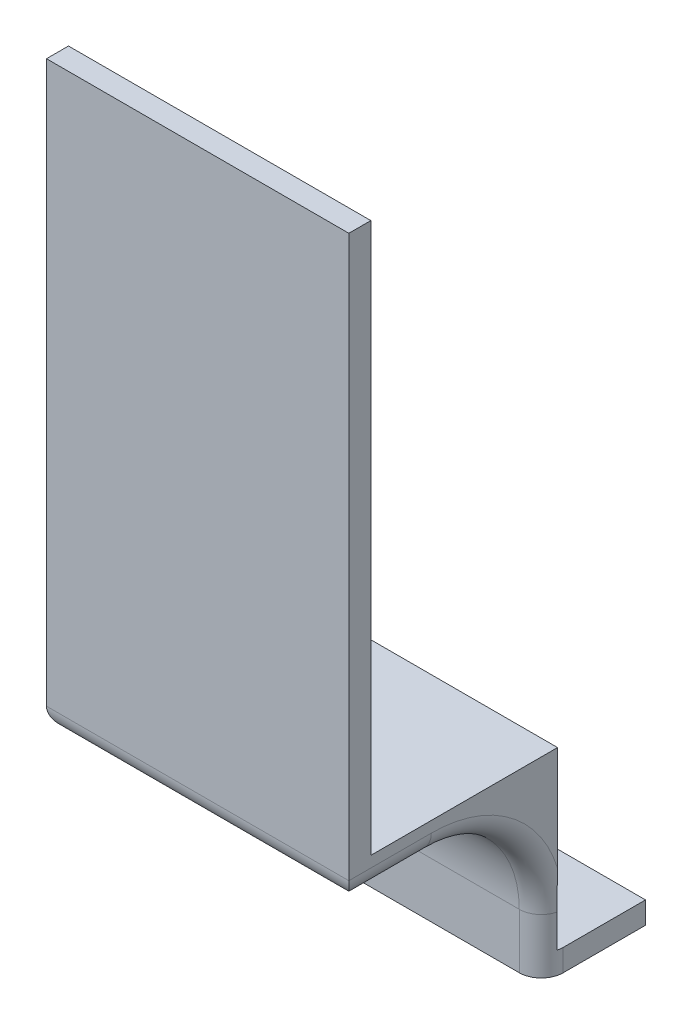
SolidWorks part; units mm, degrees
material "PET"
ref_plane "前视基准面" through (0, 0, 0) normal (0, 0, 1) x (1, 0, 0)
ref_plane "上视基准面" through (0, 0, 0) normal (0, 1, 0) x (1, 0, 0)
ref_plane "右视基准面" through (0, 0, 0) normal (1, 0, 0) x (0, 0, -1)
other "Configuration Table"
sketch "草图1" plane through (0, 0, 0) normal (0, 1, 0) x (1, 0, 0)
  line L1 (-15, 5.5) -> (15, 5.5)
  line L2 (-15, 5.5) -> (-15, -5.5)
  line L3 (-15, -5.5) -> (15, -5.5)
  line L4 (15, 5.5) -> (15, -5.5)
  line L5 (-15, 5.5) -> (15, -5.5) construction
  line L6 (-15, -5.5) -> (15, 5.5) construction
  point P0 (0, 0)
  dimension "D1" = 30
  dimension "D2" = 11
extrude "凸台-拉伸1" add sketch "草图1" along normal blind 6
sketch "草图2" plane through (-15, 0, 0) normal (-1, 0, 0) x (0, 0, 1)
  line L0 (-5.5, 6) -> (-5.5, 0) construction
  line L1 (-13.5, 2) -> (2.5, 2)
  line L2 (-13.5, 2) -> (-13.5, 4)
  line L3 (-13.5, 4) -> (2.5, 4)
  line L4 (2.5, 2) -> (2.5, 4)
  line L5 (-13.5, 2) -> (2.5, 4) construction
  line L6 (-13.5, 4) -> (2.5, 2) construction
  line L7 (-5.5, 6) -> (5.5, 6) construction
  line L8 (5.5, 6) -> (5.5, 0) construction
  point P0 (-5.5, 3)
  dimension "D1" = 2
  dimension "D2" = 3
extrude "切除-拉伸1" cut sketch "草图2" against normal blind 144
sketch "草图3" plane through (0, 6, 0) normal (0, 1, 0) x (1, 0, 0)
  line L0 (2, 5.5) -> (-2, 5.5)
  line L1 (15, 5.5) -> (-15, 5.5) construction
  line L2 (-2, 5.5) -> (-2, -3.5)
  line L3 (-2, -3.5) -> (-15, -3.5)
  line L4 (-15, 5.5) -> (-15, -5.5) construction
  line L5 (-15, -3.5) -> (-15, -5.5)
  line L6 (-15, -5.5) -> (15, -5.5)
  line L7 (-15, -5.5) -> (15, -5.5) construction
  line L8 (0, 5.5) -> (0, -5.5) construction
  line L9 (15, -3.5) -> (15, -5.5)
  line L10 (2, -3.5) -> (15, -3.5)
  line L11 (2, 5.5) -> (2, -3.5)
  dimension "D1" = 2
  dimension "D2" = 2
extrude "凸台-拉伸2" add sketch "草图3" along normal blind 50
sketch "草图4" plane through (0, 6, 0) normal (0, 1, 0) x (1, 0, 0)
  line L0 (-15, 5.5) -> (-15, 2) construction
  line L1 (-15, 5.5) -> (-15, -3.5) construction
  line L2 (-15, 2) -> (15, 2) construction
  line L3 (15, -3.5) -> (15, 5.5) construction
  line L4 (0, 5.5) -> (0, -5.5) construction
  line L5 (2, 5.5) -> (-2, 5.5) construction
  line L6 (-15, -5.5) -> (15, -5.5) construction
  circle A0 centre (-7.5, 2) radius 1.75
  circle A1 centre (7.5, 2) radius 1.75
  point P10 (0, 2)
  dimension "D2" = 7.5
  dimension "D3" = 3.5
  dimension "D1" = 3.5
extrude "切除-拉伸2" cut sketch "草图4" against normal blind 144
sketch "草图5" plane through (-15, 0, 0) normal (-1, 0, 0) x (0, 0, 1)
  line L1 (-5.5, 0) -> (5.5, 0)
  line L2 (-5.5, 0) -> (-5.5, 56)
  line L3 (-5.5, 56) -> (5.5, 56)
  line L4 (5.5, 0) -> (5.5, 56)
extrude "切除-拉伸3" cut sketch "草图5" against normal blind 2.5
sketch "草图6" plane through (0, 6, 0) normal (0, 1, 0) x (1, 0, 0)
  line L0 (-12.5, -2.5) -> (-12.5, 7.5) construction
  line L1 (-22.5, 7.5) -> (-25.5, 7.5)
  line L2 (-12.5, -2.5) -> (-12.5, -5.5)
  arc A0 (-22.5, 7.5) -> (-12.5, -2.5) centre (-12.5, 7.5) ccw
  arc A1 (-25.5, 7.5) -> (-12.5, -5.5) centre (-12.5, 7.5) ccw
  dimension "D1" = 10
sketch "草图7" plane through (-12.5, 0, 0) normal (-1, 0, 0) x (0, 0, 1)
  line L1 (-5.5, 2) -> (5.5, 2)
  line L2 (-5.5, 2) -> (-5.5, 56)
  line L3 (-5.5, 56) -> (5.5, 56)
  line L4 (5.5, 2) -> (5.5, 56)
extrude "切除-拉伸5" cut sketch "草图7" against normal blind 47
sketch "草图8" plane through (0, 2, 0) normal (0, 1, 0) x (1, 0, 0)
  line L1 (-12.5, -5.5) -> (15, -5.5)
  line L2 (-12.5, -5.5) -> (-12.5, -6.9824)
  line L3 (-12.5, -6.9824) -> (15, -6.9824)
  line L4 (15, -5.5) -> (15, -6.9824)
extrude "凸台-拉伸3" add sketch "草图8" along normal blind 16 and the other way up to surface (2 mm away) other way up to face at (7.5, 0, -0.25)
sketch "草图9" plane through (0, 2, 0) normal (0, 1, 0) x (1, 0, 0)
  line L0 (15, 5.5) -> (15, -5.5) construction
  line L1 (-12.5, -5.5) -> (15, -5.5)
  line L2 (-12.5, -5.5) -> (-12.5, -2.5)
  line L3 (-12.5, -2.5) -> (15, -2.5)
  line L4 (15, -5.5) -> (15, -2.5)
extrude "凸台-拉伸4" add sketch "草图9" along normal blind 16
sketch "草图10" plane through (15, 0, 0) normal (1, 0, 0) x (0, 0, -1)
  line L0 (-6.9824, 0) -> (5.5, 0) construction
  line L1 (-6.9824, 18) -> (-3.9824, 18)
  line L2 (-6.9824, 18) -> (-6.9824, 0)
  line L3 (-6.9824, 0) -> (-3.9824, 0)
  line L4 (-3.9824, 18) -> (-3.9824, 0)
  dimension "D1" = 3
extrude "切除-拉伸6" cut sketch "草图10" against normal blind 47
sketch "草图12" plane through (0, 0, 3.9824) normal (0, 0, 1) x (1, 0, 0)
  line L0 (15, 0) -> (15, 18) construction
  line L1 (-12.5, 18) -> (15, 18)
  line L2 (-12.5, 18) -> (-12.5, 15)
  line L3 (-12.5, 15) -> (15, 15)
  line L4 (15, 18) -> (15, 15)
  dimension "D1" = 3
extrude "凸台-拉伸5" add sketch "草图12" along normal blind 15.5
sketch "草图13" plane through (0, 15, 0) normal (0, -1, 0) x (-1, 0, 0)
  line L1 (12.5, -19.4824) -> (-15, -19.4824)
  line L2 (12.5, -19.4824) -> (12.5, -21.4824)
  line L3 (12.5, -21.4824) -> (-15, -21.4824)
  line L4 (-15, -19.4824) -> (-15, -21.4824)
  dimension "D1" = 2
extrude "凸台-拉伸6" add sketch "草图13" against normal blind 53
ref_plane "基准面1" through (0, 41.5, 0) normal (0, -1, 0) x (-1, 0, 0)
sketch "草图14" plane through (0, 68, 0) normal (0, 1, 0) x (1, 0, 0)
  line L1 (-12.5, -21.4824) -> (15, -21.4824)
  line L2 (-12.5, -21.4824) -> (-12.5, -2.5)
  line L3 (-12.5, -2.5) -> (15, -2.5)
  line L4 (15, -21.4824) -> (15, -2.5)
extrude "凸台-拉伸7" add sketch "草图14" along normal blind 3
sketch "草图15" plane through (0, 71, 0) normal (0, 1, 0) x (1, 0, 0)
  line L5 (15, -21.4824) -> (15, -2.5) construction
  line L6 (-12.5, -2.5) -> (15, -2.5)
  line L7 (-12.5, -2.5) -> (-12.5, -4.5)
  line L8 (-12.5, -4.5) -> (15, -4.5)
  line L9 (15, -2.5) -> (15, -4.5)
  dimension "D1" = 2
extrude "凸台-拉伸8" add sketch "草图15" along normal blind 13
sketch "草图16" plane through (0, 84, 0) normal (0, 1, 0) x (1, 0, 0)
  line L1 (-12.5, -4.5) -> (15, -4.5)
  line L2 (-12.5, -4.5) -> (-12.5, 5.5)
  line L3 (-12.5, 5.5) -> (15, 5.5)
  line L4 (15, -4.5) -> (15, 5.5)
extrude "凸台-拉伸9" add sketch "草图16" along normal blind 2
sketch "草图17" plane through (0, 84, 0) normal (0, -1, 0) x (-1, 0, 0)
  circle A0 centre (7.5, 2) radius 1.75
  circle A1 centre (-7.5, 2) radius 1.75
extrude "切除-拉伸8" cut sketch "草图17" against normal blind 6
fillet "圆角1" radius 10 2 edges at (1.25, 71, 4.5) (1.25, 15, 3.9824)
fillet "圆角2" radius 2 14 edges at (-12.5, 83.5, 4.5) (-12.5, 73.9289, 7.4289) (15, 83.5, 4.5) (15, 73.9289, 7.4289) (15, 2.5, 3.9824) (15, 12.0711, 6.9113) (-12.5, 2.5, 3.9824) (-12.5, 12.0711, 6.9113) (1.25, 71, 21.4824) (-12.5, 71, 17.9912) (15, 71, 17.9912) (1.25, 15, 21.4824) (15, 15, 17.7324) (-12.5, 15, 17.7324)
sketch "草图18" plane through (15, 0, 0) normal (1, 0, 0) x (0, 0, -1)
  line L0 (-21.4824, 68) -> (12.3986, 68)
  line L1 (-21.4824, 69) -> (-21.4824, 17) construction
  line L4 (-21.4824, 68) -> (-21.4824, 90.6748)
  line L5 (-21.4824, 90.6748) -> (12.3986, 90.6748)
  line L6 (12.3986, 68) -> (12.3986, 90.6748)
  line M1 (-2.5, 68) -> (-2.5, 81)
  arc M2 (-2.5, 81) -> (-14.5, 69) centre (-14.5, 81) cw
  line M3 (-14.5, 69) -> (-21.4824, 69)
extrude "切除-拉伸9" cut sketch "草图18" against normal blind 63 contours L0 L6 L5 L4 M3 M2 M1 region at (15, 79.9531, 4.3176)
sketch "草图19" plane through (15, 0, 0) normal (1, 0, 0) x (0, 0, -1)
  line L1 (-2.5, 68) -> (-21.4824, 68)
  line L2 (-2.5, 68) -> (-2.5, 84.8214)
  line L3 (-2.5, 84.8214) -> (-21.4824, 84.8214)
  line L4 (-21.4824, 68) -> (-21.4824, 84.8214)
extrude "切除-拉伸10" cut sketch "草图19" against normal blind 63
